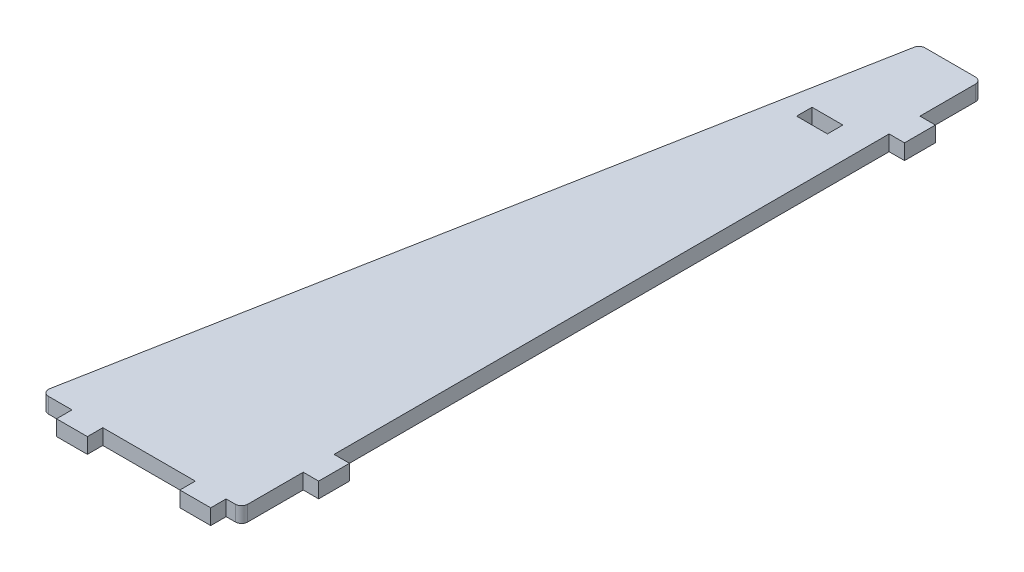
SolidWorks part; units mm, degrees
material "Beech"
ref_plane "Front Plane" through (0, 0, 0) normal (0, 0, 1) x (1, 0, 0)
ref_plane "Top Plane" through (0, 0, 0) normal (0, 1, 0) x (1, 0, 0)
ref_plane "Right Plane" through (0, 0, 0) normal (1, 0, 0) x (0, 0, -1)
sketch "Sketch1" plane through (0, 0, 0) normal (0, 1, 0) x (1, 0, 0)
  line L0 (0, 0) -> (12.7, 0)
  line L1 (12.7, 0) -> (12.7, -6.35)
  line L2 (12.7, -6.35) -> (25.4, -6.35)
  line L3 (25.4, -6.35) -> (25.4, 0)
  line L4 (25.4, 0) -> (63.5, 0)
  line L5 (63.5, 0) -> (63.5, -6.35)
  line L6 (63.5, -6.35) -> (76.2, -6.35)
  line L7 (76.2, -6.35) -> (76.2, 0)
  line L8 (76.2, 0) -> (82.55, 0)
  line L9 (82.55, 0) -> (82.55, 25.4)
  line L10 (82.55, 304.8) -> (57.15, 304.8)
  line L11 (57.15, 304.8) -> (0, 0)
  line L12 (82.55, 25.4) -> (88.9, 25.4)
  line L13 (88.9, 25.4) -> (88.9, 38.1)
  line L14 (88.9, 38.1) -> (82.55, 38.1)
  line L15 (82.55, 38.1) -> (82.55, 266.7)
  line L16 (82.55, 266.7) -> (88.9, 266.7)
  line L17 (88.9, 266.7) -> (88.9, 279.4)
  line L18 (88.9, 279.4) -> (82.55, 279.4)
  line L19 (82.55, 279.4) -> (82.55, 304.8)
  line L20 (57.15, 260.35) -> (57.15, 254)
  line L21 (57.15, 260.35) -> (69.85, 260.35)
  line L22 (57.15, 254) -> (69.85, 254)
  line L23 (69.85, 260.35) -> (69.85, 254)
  dimension "D1" = 12.7
  dimension "D2" = 6.35
  dimension "D3" = 25.4
  dimension "D4" = 50.8
  dimension "D5" = 12.7
  dimension "D6" = 304.8
  dimension "D7" = 25.4
  dimension "D8" = 25.4
  dimension "D9" = 6.35
  dimension "D10" = 254
  dimension "D11" = 6.35
  dimension "D12" = 12.7
  dimension "D13" = 12.7
extrude "Boss-Extrude1" add sketch "Sketch1" along normal blind 6.35
fillet "Fillet1" radius 2.54 4 edges at (82.55, 3.175, 0) (82.55, 3.175, -304.8) (57.15, 3.175, -304.8) (0, 3.175, 0)
equation "\"CageLeftBottomEdge\"=22.11mm"
equation "\"CageLeftTopEdge\"=22.11mm"
equation "\"CageRightBottomEdge\"=21.63mm"
equation "\"CageRightTopEdge\"=21.63mm"
equation "\"CageHeight\"=86.04mm"
equation "\"CageLength\"=73.76mm"
equation "\"CageTopScrewClearance\"=10mm"
equation "\"CageBottomScrewClearance\"=25mm"
equation "\"CageLeftTopDepth\"= 11.65mm"
equation "\"CageLeftBottomDepth\"=11.11mm"
equation "\"CageLeftTopHeight\"=8.56175mm"
equation "\"CageLeftBottomHeight\"=16mm"
equation "\"CageRightTopDepth\"= 11.05mm"
equation "\"CageRightBottomDepth\"=10.58mm"
equation "\"CageRightTopHeight\"=9.6mm"
equation "\"CageRightBottomHeight\"=15.49mm"
equation "\"CageLeftTopChannelDepth\"=2.41908mm"
equation "\"CageLeftBottomChannelDepth\"=2.588mm"
equation "\"CageLeftChannelHeight\"=11.7mm"
equation "\"CageRightTopChannelDepth\"=2.32mm"
equation "\"CageRightBottomChannelDepth\"=2.318mm"
equation "\"CageRightChannelHeight\"=10mm"
equation "\"CageChanRelHeight\"=23.99mm"
equation "\"CageChanRelDepth\"=5.492mm"
equation "\"CageChamberRadius\"=16.261mm"
equation "\"CageScrewDiameter\"=4.8mm"
equation "\"CageSetScrewDiameter\"=3.5mm"
equation "\"CageAxleRadius\"=6.639mm"
equation "\"CageAxleKeyHeight\"=1.619mm"
equation "\"CageAxleKeyWidth\"=2.662mm"
equation "\"CageHoseWindowWidth\"=16.29mm"
equation "\"CageHoseWindowHeight\"=26.5mm"
equation "\"CageHoseWindow-Edge\"=8.89mm"
equation "\"CageScrew-VerticalEdge\"=5.0mm"
equation "\"CageScrew-HorizontalEdge\"=7.5mm"
equation "\"CageScrew-HoseCornerScrewEdge\"=4.45mm"
equation "\"CageAxle-BottomEdge\"=56.05mm"
equation "\"CageAxle-FrontEdge\"=46.03mm"
equation "\"CageBackSetScrew-Axle\"=40mm"
equation "\"CageFrontSetScrew-Axle\"=22mm"
equation "\"CageVelocityWindow-BackEdge\"=34.8mm"
equation "\"CageVelocityWindow-BottomEdge\"=27.55mm"
equation "\"CageVelocityWindowHeight\"=22.29mm"
equation "\"CageVelocityWindowWidth\"=12.61mm"
equation "\"TriggerSlot-BottomEdge\"=6.35mm"
equation "\"TriggerSlot-FrontEdge\"=15mm"
equation "\"TriggerSlotSize\"=6.7mm"
equation "\"TriggerRackOffset\"=.236224in"
equation "\"TriggerSlotSizeInt\"=.25in"
equation "\"MotorMountLegLength\"=.25in"
equation "\"GearOffset\"=.264907in"
equation "\"TriggerSlotSpacing\"=.25in"
equation "\"TriggerMiniSlotWidth\"=3.5mm"
equation "\"TriggerRackWidth\"=6.5mm"
equation "\"TGMGearFaceDiameter\"=24.40mm"
equation "\"TGMCylinderLength\"=15.00mm"
equation "\"TGMScrewHole-Center\"=8.70mm"
equation "\"TGMScrewHoleDiameter\"=5.04mm"
equation "\"TGMCenterHoleDiameter\"=9.50mm"
equation "\"TGMShaftCollarSideLength\"=19.00mm"
equation "\"TGMShaftCollarDockingDepth\"=7.00mm"
equation "\"whitemotordepth\"=11.27mm"
equation "\"whitemotorbackdepth\"=3.845mm"
equation "\"whitemotoraxledepth\" = 3.5mm"
equation "\"whitemotoraxleoffset\"=11.4mm"
equation "\"whitemotorwidth\"=12.07mm"
equation "\"whitemotorheight\"=16.68mm"
equation "\"whitemotorcylinderlength\" =13.04mm"
equation "\"whitemotorcylinderradius\"=3.845mm"
equation "\"whitemotorcylinderoffset\"=2.35mm"
equation "\"whitemotorcutoutlength\"=1.88mm"
equation "\"whitemotorouterrad\"=5mm"
equation "\"whitemotorinnerrad\"=2.95mm"
equation "\"elasticracklength\"=2in"
equation "\"elasticrackpegsize\"=.25in"
equation "\"elasticrackpegbuffer\"=.125in"
equation "\"elasticrackpegspacing\"=1.76476378in"
equation "\"elasticbaybuffer\"=.25in"
equation "\"elasticdepth\"=.125in"
equation "\"elasticbaydepth\"=.75in"
equation "\"motormountwidth\"=12mm"
equation "\"motormountcornerfillet\"=3mm"
equation "\"pandiscradius\"=14in"
equation "\"towermaterialwidth\"=.25in"
equation "\"towerslotlength\"=.5in"
equation "\"towermarkerspace\"=5in"
equation "\"towerslothorizoffset\"=1in"
equation "\"towerslothorizspacing\"=2in"
equation "\"towerslotvertoffset\"=3in"
equation "\"D1@Sketch1\"=\"towerslotlength\""
equation "\"D2@Sketch1\"=\"towermaterialwidth\""
equation "\"towerupslot\"=1in"
equation "\"D3@Sketch1\"=\"towerupslot\""
equation "\"towerslotvertspacing\"=2in"
equation "\"D4@Sketch1\"=\"towerslotvertspacing\""
equation "\"D5@Sketch1\"=\"towerslotlength\""
equation "\"towerheight\"=12in"
equation "\"D6@Sketch1\"=\"towerheight\""
equation "\"D7@Sketch1\"=\"towerslotlength\"*2"
equation "\"D8@Sketch1\"=\"towerupslot\""
equation "\"D9@Sketch1\"=\"towerslotvertoffset\"-(\"towermarkerspace\"/2)-\"towermaterialwidth\""
equation "\"towermotorpanelheight\"=10in"
equation "\"D10@Sketch1\"=\"towermotorpanelheight\""
equation "\"D11@Sketch1\"=\"towermaterialwidth\""
equation "\"D12@Sketch1\"=\"towerslotlength\""
equation "\"D13@Sketch1\"=\"towerslotlength\""
equation "\"D1@Boss-Extrude1\"=\"towermaterialwidth\""
equation "\"toweraxle\"=.5in"
equation "\"towerplatslotoffset\"=1.5in"
equation "\"towerplatdepth\"=2in"
equation "\"stepperouterrad\"=10mm"
equation "\"stepperscrewsize\"=3.45mm"
equation "\"stepperscrewc2c\"=49.5mm"
equation "\"stepperdepthoffset\"=24mm"
equation "\"stepperhorizoffset\"=22.91mm"
equation "\"shaftslotOD\"=18.8mm"
equation "\"shaftslotID\"=13.28mm"
equation "\"shaftkeywidth\"=2.67mm"
equation "\"shaftkeydepth\"=1.8mm"
equation "\"shaftcollartotaldepth\"=12.5mm"
equation "\"shaftsquaredepth\"=6mm"
equation "\"shaftsetscrewsize\"=3.5mm"
equation "\"shaftkeytightdepth\"=1.85mm"
equation "\"shaftslottightID\"=12.78mm"
equation "\"shaftsetscrewoffset\"=9mm"
equation "\"cagecollartotaldepth\"=10mm"
equation "\"cagecollartotalwidth\"=35mm"
equation "\"cagecollarbasedepth\"=4mm"
